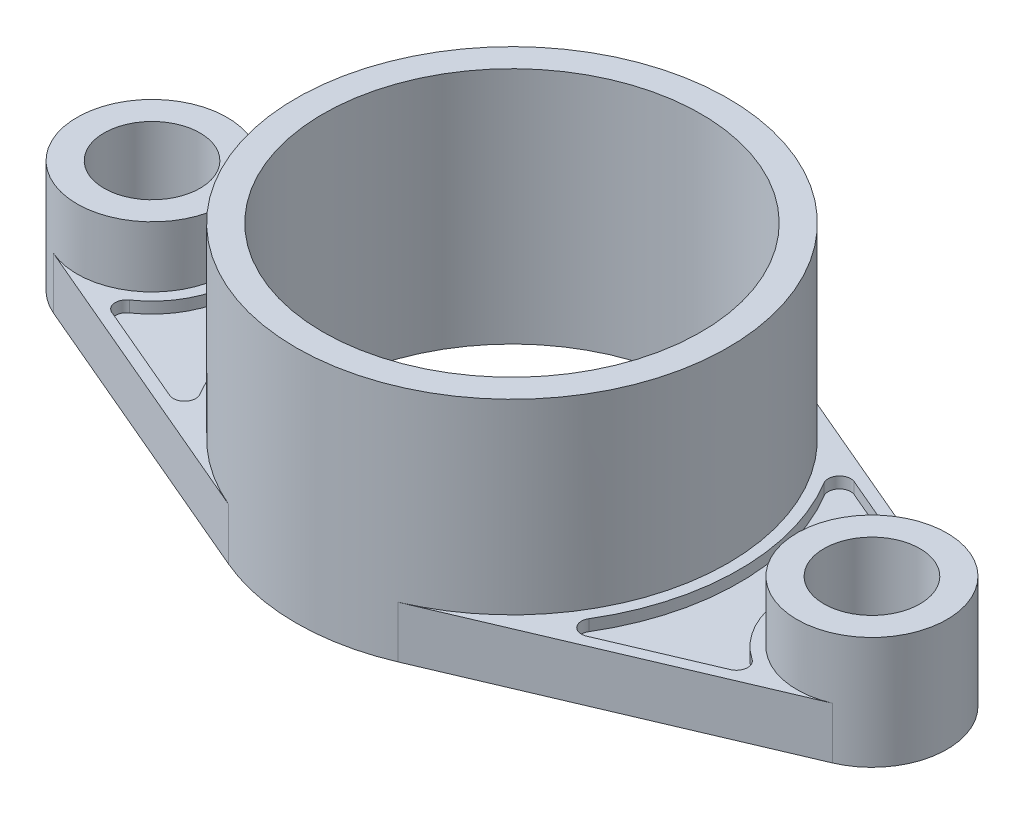
SolidWorks part; units mm, degrees
material "Polybutadiene (PB)"
ref_plane "Front Plane" through (0, 0, 0) normal (0, 0, 1) x (1, 0, 0)
ref_plane "Top Plane" through (0, 0, 0) normal (0, 1, 0) x (1, 0, 0)
ref_plane "Right Plane" through (0, 0, 0) normal (1, 0, 0) x (0, 0, -1)
sketch "Sketch1" plane through (0, 0, 0) normal (0, 1, 0) x (1, 0, 0)
  line L0 (-86.5278, 15.3351) -> (-18.8, 44.1651)
  line L1 (-86.5278, -15.3351) -> (-18.8, -44.1651)
  line L2 (86.5278, 15.3351) -> (18.8, 44.1651)
  line L3 (86.5278, -15.3351) -> (18.8, -44.1651)
  line L4 (0, 0) -> (-80, 0) construction
  circle A0 centre (0, 0) radius 48
  circle A1 centre (-80, 0) radius 10.6667
  circle A2 centre (80, 0) radius 10.6667
  circle A3 centre (-80, 0) radius 16.6667
  circle A4 centre (80, 0) radius 16.6667
  circle A5 centre (0, 0) radius 42
  dimension "D2" = 21.3333
  dimension "D3" = 96
  dimension "D4" = 33.3333
  dimension "D1" = 160
  dimension "D5" = 6
extrude "Boss-Extrude1" add sketch "Sketch1" along normal blind 11.5 contours A3 A1 | L4 A0 L0 A3 | A0 L4 A3 L1 | A4 L2 A0 L3 | A4 A2 | A5 A0 region at (-54.8023, 0, -17.8948) region at (-71.0681, 0, -13.5095) region at (0, 0, -46.6424) region at (-54.8023, 0, 17.8948) region at (54.8023, 0, 0) region at (93.5095, 0, -8.9319)
extrude "Boss-Extrude2" add sketch "Sketch1<3>" along normal blind 25 contours A3 A1 | A4 A2 region at (-71.0681, 0, -13.5095) region at (93.5095, 0, -8.9319)
sketch "Sketch1<3>" plane through (0, 0, 0) normal (0, 1, 0) x (1, 0, 0) same geometry as "Sketch1"
extrude "Boss-Extrude3" add sketch "Sketch1<4>" along normal blind 53 contours A5 A0 region at (0, 0, -46.6424)
sketch "Sketch1<4>" plane through (0, 0, 0) normal (0, 1, 0) x (1, 0, 0) same geometry as "Sketch1"
sketch "Sketch2" plane through (0, 11.5, 0) normal (0, 1, 0) x (1, 0, 0)
  line L4 (-73.6701, -18.0912) -> (-37.9794, -33.2839)
  line L5 (-37.9794, 33.2839) -> (-73.6701, 18.0912)
  line L6 (-68.7498, -20.1857) -> (-46.3293, -29.7295)
  line L7 (-46.3293, 29.7295) -> (-68.7498, 20.1857)
  arc A2 (-46.3293, -29.7295) -> (-43.211, -26.1354) centre (-45.3501, -27.4293) ccw
  arc A3 (-68.7498, -20.1857) -> (-69.1817, -15.8217) centre (-67.7707, -17.8854) cw
  arc A4 (-37.9794, 33.2839) -> (-37.9794, -33.2839) centre (0, 0) ccw
  arc A5 (-73.6701, -18.0912) -> (-73.6701, 18.0912) centre (-80, 0) ccw
  arc A6 (-43.211, 26.1354) -> (-43.211, -26.1354) centre (0, 0) ccw
  arc A7 (-69.1817, -15.8217) -> (-69.1817, 15.8217) centre (-80, 0) ccw
  arc A8 (-43.211, 26.1354) -> (-46.3293, 29.7295) centre (-45.3501, 27.4293) ccw
  arc A9 (-68.7498, 20.1857) -> (-69.1817, 15.8217) centre (-67.7707, 17.8854) ccw
  dimension "D2" = 2.5
  dimension "D1" = 2.5
extrude "Cut-Extrude1" cut sketch "Sketch2" against normal blind 2.5
mirror "Mirror1" about plane through (0, 0, 0) normal (1, 0, 0) of "Cut-Extrude1"
equation "\"A\" = 32"
equation "\"B\" = 6"
equation "\"C\"= 2.5"
equation "\"D1@Sketch1\"=\"A\"*5"
equation "\"D2@Sketch1\"=\"A\"*2/3"
equation "\"D3@Sketch1\"=\"A\"*3"
equation "\"D4@Sketch1\"=\"D2@Sketch1\"+2*\"B\""
equation "\"D5@Sketch1\"=\"B\""
equation "\"D1@Sketch2\"=\"C\""
equation "\"D2@Sketch2\"=\"C\""
equation "\"D1@Cut-Extrude1\"=\"C\""
equation "\"D1@Boss-Extrude1\"=9+\"C\""
